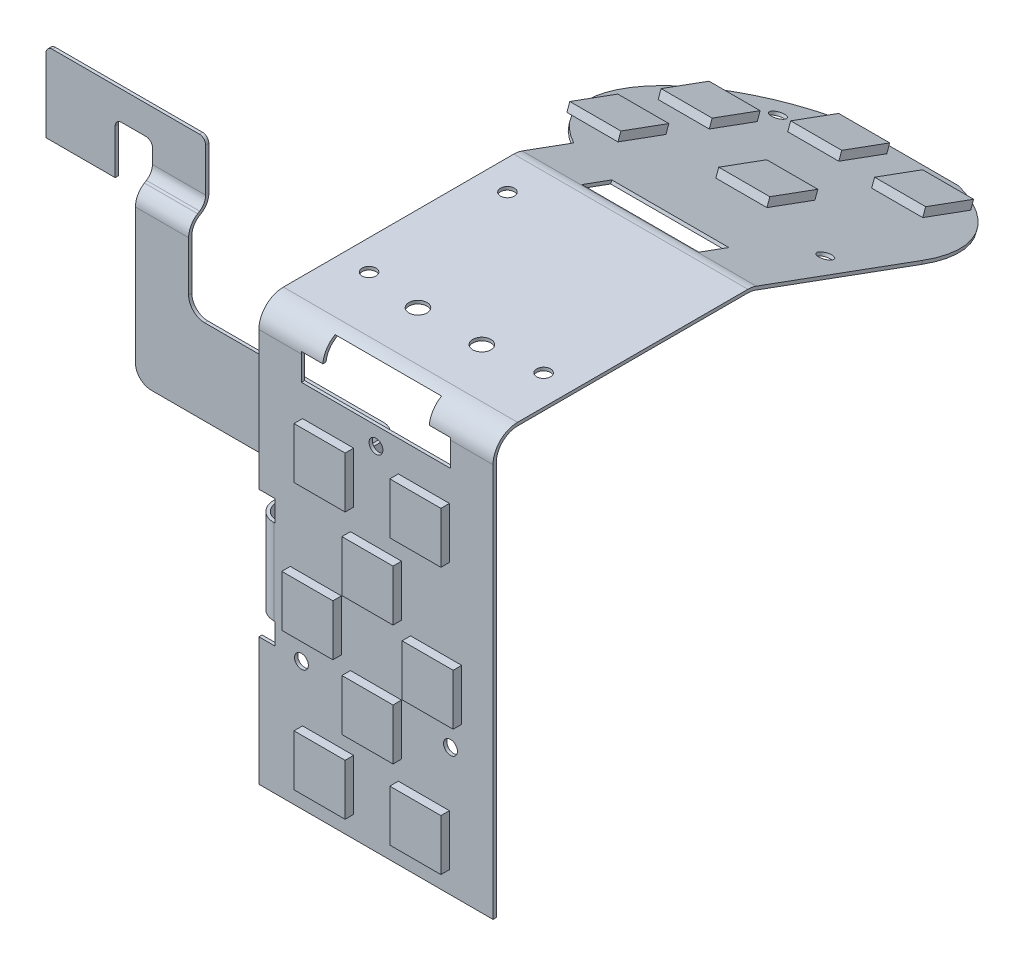
SolidWorks part; units mm, degrees
ref_plane "前视基准面" through (0, 0, 0) normal (0, 0, 1) x (1, 0, 0)
ref_plane "上视基准面" through (0, 0, 0) normal (0, 1, 0) x (1, 0, 0)
ref_plane "右视基准面" through (0, 0, 0) normal (1, 0, 0) x (0, 0, -1)
other "Configuration Table"
sketch "草图1" plane through (0, 0, 0) normal (1, 0, 0) x (0, 0, -1)
  line L0 (0, -25) -> (0, -2)
  line L1 (2, 0) -> (23.6457, 0)
  line L2 (24.3327, -0.1217) -> (52.1746, -10.3049)
  line L3 (-0.3, -25) -> (-0.3, -2)
  line L4 (2, 0.3) -> (23.6457, 0.3)
  line L5 (24.4358, 0.1601) -> (52.2777, -10.0231)
  line L6 (0, -25) -> (-0.3, -25)
  line L7 (52.2777, -10.0231) -> (52.1746, -10.3049)
  arc A0 (23.6457, 0) -> (24.3327, -0.1217) centre (23.6457, -2) cw
  arc A1 (0, -2) -> (2, 0) centre (2, -2) cw
  arc A2 (-0.3, -2) -> (2, 0.3) centre (2, -2) cw
  arc A3 (23.6457, 0.3) -> (24.4358, 0.1601) centre (23.6457, -2) cw
  point P7 (24, 0)
  point P10 (0, 0)
  dimension "D5" = 2
  dimension "D1" = 25
  dimension "D2" = 24
  dimension "D3" = 159.91
  dimension "D4" = 30
  dimension "D6" = 0.3
extrude "凸台-拉伸1" add sketch "草图1" along normal blind 22
sketch "草图2" plane through (0, 0, 0.3) normal (0, 0, 1) x (1, 0, 0)
  line L0 (22, 0.3) -> (0, 0.3) construction
  line L1 (4, -4.3) -> (18, -4.3)
  line L2 (4, -4.3) -> (4, -1.8)
  line L3 (4, -1.8) -> (18, -1.8)
  line L4 (18, -4.3) -> (18, -1.8)
  line L5 (6, -1.8) -> (16, -1.8)
  line L6 (6, -1.8) -> (6, 0)
  line L7 (6, 0) -> (16, 0)
  line L8 (16, -1.8) -> (16, 0)
  line L10 (11, -26.5654) -> (11, 3.7124) construction
  line L12 (0, -2) -> (0, -25) construction
  line L13 (22, -2) -> (22, -25) construction
  line M13 (22, -2) -> (0, -2)
  dimension "D1" = 1.8
  dimension "D2" = 2.5
  dimension "D3" = 0.3
  dimension "D4" = 14
  dimension "D5" = 10
extrude "切除-拉伸1" cut sketch "草图2" against normal blind 4 contours L3 L10 L7 L6 | L10 L5 L8 L7 | L1 L10 L2 M13 | L10 L1 L4 M13 | L10 L3 L2 M13 | L10 L4 L3 L5 M13 region at (7.5, -3.15, 0.3) region at (14.5, -3.15, 0.3) region at (7.5, -1.9, 0.3) region at (14.5, -1.9, 0.3) region at (13.5, -0.9, 0.3) region at (8.5, -0.9, 0.3)
sketch "草图3" plane through (0, 8.024, -2.9348) normal (0, 0.9392, -0.3435) x (1, 0, 0)
  line L0 (22, 52.5397) -> (22, 22.894) construction
  line L1 (22, 52.5397) -> (0, 52.5397) construction
  circle A0 centre (8, 39.5397) radius 14
  line M2 (0, 52.5397) -> (0, 22.894)
  line M4 (22, 22.894) -> (22, 52.5397)
  line M5 (22, 52.5397) -> (0, 52.5397)
  dimension "D1" = 28
  dimension "D2" = 13
extrude "切除-拉伸2" cut sketch "草图3" against normal through all contours A0 M4 M5 | A0 M5 M2 region at (19.6053, -8.9881, -49.4478) region at (0.8895, -9.8577, -51.8254)
extrude "凸台-拉伸2" add sketch "草图3<3>" against normal blind 0.3
sketch "草图3<3>" plane through (0, 8.024, -2.9348) normal (0, 0.9392, -0.3435) x (1, 0, 0) same geometry as "草图3"
sketch "草图4" plane through (0, 0, 0.3) normal (0, 0, 1) x (1, 0, 0)
  line L0 (-5.9466, -22.2) -> (23.7502, -22.2) construction
  line L1 (8.6, -14.15) -> (13.4, -14.15)
  line L2 (8.6, -14.15) -> (8.6, -18.95)
  line L3 (8.6, -18.95) -> (13.4, -18.95)
  line L4 (13.4, -14.15) -> (13.4, -18.95)
  line L5 (11, -28.2671) -> (11, 2.5503) construction
  line L6 (0, -2) -> (0, -25) construction
  line L7 (22, -2) -> (22, -25) construction
  line L8 (22, -25) -> (0, -25) construction
  line L9 (8.6, -25.45) -> (13.4, -25.45)
  line L10 (8.6, -25.45) -> (8.6, -30.25)
  line L11 (8.6, -30.25) -> (13.4, -30.25)
  line L12 (13.4, -25.45) -> (13.4, -30.25)
  line L14 (2.95, -19.8) -> (7.75, -19.8)
  line L15 (2.95, -19.8) -> (2.95, -24.6)
  line L16 (2.95, -24.6) -> (7.75, -24.6)
  line L17 (7.75, -19.8) -> (7.75, -24.6)
  line L18 (14.25, -19.8) -> (19.05, -19.8)
  line L19 (14.25, -19.8) -> (14.25, -24.6)
  line L20 (14.25, -24.6) -> (19.05, -24.6)
  line L21 (19.05, -19.8) -> (19.05, -24.6)
  dimension "D1" = 4.8
  dimension "D2" = 2.8
  dimension "D3" = 6.5
  dimension "D4" = 6.5
extrude "凸台-拉伸3" add sketch "草图4" along normal blind 0.8
sketch "草图5" plane through (0, 0.3, 0) normal (0, 1, 0) x (1, 0, 0)
  line L0 (11, -6.2283) -> (11, 16.6274) construction
  line L3 (0, 23.6457) -> (0, 2) construction
  line L4 (22, 23.6457) -> (22, 2) construction
  line L5 (22, 23.6457) -> (0, 23.6457) construction
  circle A0 centre (8, 6.6457) radius 0.85
  circle A1 centre (14, 6.6457) radius 0.85
  dimension "D1" = 1.7
  dimension "D2" = 17
  dimension "D3" = 3
extrude "切除-拉伸3" cut sketch "草图5" against normal through all
sketch "草图6" plane through (0, 8.024, -2.9348) normal (0, 0.9392, -0.3435) x (1, 0, 0)
  line L0 (11, 16.3664) -> (11, 30.7303) construction
  line L1 (5.5, 23) -> (16.5, 23)
  line L2 (5.5, 23) -> (5.5, 26)
  line L3 (5.5, 26) -> (16.5, 26)
  line L4 (16.5, 23) -> (16.5, 26)
  line L7 (0, 22.1039) -> (0, 1.7753) construction
  line L8 (22, 22.1039) -> (22, 1.7753) construction
  dimension "D1" = 11
  dimension "D2" = 3
  dimension "D3" = 23
extrude "切除-拉伸4" cut sketch "草图6" against normal blind 1
sketch "草图7" plane through (0, 8.024, -2.9348) normal (0, 0.9392, -0.3435) x (1, 0, 0)
  line L1 (7.3385, 34.4514) -> (12.1385, 34.4514)
  line L2 (7.3385, 34.4514) -> (7.3385, 39.2514)
  line L3 (7.3385, 39.2514) -> (12.1385, 39.2514)
  line L4 (12.1385, 34.4514) -> (12.1385, 39.2514)
  line L5 (11.7188, 45.3744) -> (16.5188, 45.3744)
  line L6 (11.7188, 45.3744) -> (11.7188, 50.1744)
  line L7 (11.7188, 50.1744) -> (16.5188, 50.1744)
  line L8 (16.5188, 45.3744) -> (16.5188, 50.1744)
  line L9 (7.6196, 46.4557) -> (2.8196, 46.4557)
  line L10 (7.6196, 46.4557) -> (7.6196, 51.2557)
  line L11 (7.6196, 51.2557) -> (2.8196, 51.2557)
  line L12 (2.8196, 46.4557) -> (2.8196, 51.2557)
  line L13 (0.9105, 40.6376) -> (-3.8895, 40.6376)
  line L14 (0.9105, 40.6376) -> (0.9105, 45.4376)
  line L15 (0.9105, 45.4376) -> (-3.8895, 45.4376)
  line L16 (-3.8895, 40.6376) -> (-3.8895, 45.4376)
  line L17 (0.748, 31.6791) -> (-4.052, 31.6791)
  line L18 (0.748, 31.6791) -> (0.748, 36.4791)
  line L19 (0.748, 36.4791) -> (-4.052, 36.4791)
  line L20 (-4.052, 31.6791) -> (-4.052, 36.4791)
  dimension "D1" = 4.8
extrude "凸台-拉伸4" add sketch "草图7" along normal blind 0.8
sketch "草图9" plane through (0, -25, 0) normal (0, -1, 0) x (1, 0, 0)
  line L0 (22, 0.3) -> (0, 0.3) construction
  line L1 (0, 0) -> (1.5, 0)
  line L2 (0, 0) -> (0, 0.3)
  line L3 (0, 0.3) -> (1.5, 0.3)
  line L4 (1.5, 0) -> (1.5, 0.3)
  dimension "D1" = 1.5
extrude "切除-拉伸5" cut sketch "草图9" against normal blind 10
sketch "草图10" plane through (0, -25, 0) normal (0, -1, 0) x (1, 0, 0)
  line L0 (1.5, 0) -> (1.4, 0)
  line L1 (-0.1, -1.5) -> (-0.1, -11.5)
  line L2 (-1.6, -13) -> (-17.6, -13)
  line L3 (1.5, 0.3) -> (1.4, 0.3)
  line L4 (-0.4, -1.5) -> (-0.4, -11.5)
  line L5 (-1.6, -12.7) -> (-17.6, -12.7)
  line L6 (1.5, 0) -> (1.5, 0.3)
  line L7 (-17.6, -13) -> (-17.6, -12.7)
  arc A0 (1.4, 0) -> (-0.1, -1.5) centre (1.4, -1.5) ccw
  arc A1 (-0.1, -11.5) -> (-1.6, -13) centre (-1.6, -11.5) cw
  arc A2 (1.4, 0.3) -> (-0.4, -1.5) centre (1.4, -1.5) ccw
  arc A3 (-0.4, -11.5) -> (-1.6, -12.7) centre (-1.6, -11.5) cw
  point P8 (-0.1, 0)
  point P11 (-0.1, -13)
  dimension "D3" = 1.5
  dimension "D1" = 1.6
  dimension "D2" = 13
  dimension "D5" = 16
  dimension "D4" = 0.3
extrude "凸台-拉伸5" add sketch "草图10" against normal blind 8
sketch "草图11" plane through (0, 0, -12.7) normal (0, 0, 1) x (1, 0, 0)
  line L0 (-17.6, -17) -> (-17.6, -25)
  line L1 (-17.6, -25) -> (-23.1, -25)
  line L2 (-24.6, -23.5) -> (-24.6, -11)
  line L3 (-24.6, -11) -> (-19.6, -11)
  line L4 (-19.6, -11) -> (-19.6, -15.5)
  line L5 (-18.1, -17) -> (-17.6, -17)
  arc A0 (-23.1, -25) -> (-24.6, -23.5) centre (-23.1, -23.5) cw
  arc A1 (-19.6, -15.5) -> (-18.1, -17) centre (-18.1, -15.5) ccw
  point P10 (-24.6, -25)
  dimension "D4" = 1.5
  dimension "D1" = 7
  dimension "D2" = 14
  dimension "D3" = 5
extrude "凸台-拉伸6" add sketch "草图11" against normal blind 0.3
sketch "草图12" plane through (-24.6, 0, 0) normal (-1, 0, 0) x (0, 0, 1)
  line L0 (-13, -11) -> (-13, -10.8314)
  line L1 (-13.705, -9.5594) -> (-13.895, -9.4406)
  line L2 (-14.6, -8.1686) -> (-14.6, -8)
  line L3 (-12.7, -11) -> (-12.7, -10.8314)
  line L4 (-13.546, -9.305) -> (-13.736, -9.1862)
  line L5 (-14.3, -8.1686) -> (-14.3, -8)
  line L6 (-13, -11) -> (-12.7, -11)
  line L7 (-14.6, -8) -> (-14.3, -8)
  arc A0 (-13, -10.8314) -> (-13.705, -9.5594) centre (-14.5, -10.8314) ccw
  arc A1 (-13.895, -9.4406) -> (-14.6, -8.1686) centre (-13.1, -8.1686) cw
  arc A2 (-12.7, -10.8314) -> (-13.546, -9.305) centre (-14.5, -10.8314) ccw
  arc A3 (-13.736, -9.1862) -> (-14.3, -8.1686) centre (-13.1, -8.1686) cw
  point P8 (-13, -10)
  point P11 (-14.6, -9)
  dimension "D5" = 1.5
  dimension "D1" = 1
  dimension "D2" = 1
  dimension "D3" = 1.6
  dimension "D4" = 1
  dimension "D6" = 0.3
extrude "凸台-拉伸7" add sketch "草图12" against normal blind 5
sketch "草图13" plane through (0, 0, -14.3) normal (0, 0, 1) x (1, 0, 0)
  line L0 (-24.6, -8) -> (-19.6, -8)
  line L1 (-19.6, -8) -> (-19.6, -4.1)
  line L2 (-20.2, -3.5) -> (-34, -3.5)
  line L3 (-34.6, -4.1) -> (-34.6, -11)
  line L4 (-34.6, -11) -> (-28.1, -11)
  line L5 (-28.1, -11) -> (-28.1, -6.8)
  line L6 (-27.5, -6.2) -> (-25.2, -6.2)
  line L7 (-24.6, -6.8) -> (-24.6, -8)
  arc A0 (-34, -3.5) -> (-34.6, -4.1) centre (-34, -4.1) ccw
  arc A1 (-19.6, -4.1) -> (-20.2, -3.5) centre (-20.2, -4.1) ccw
  arc A2 (-25.2, -6.2) -> (-24.6, -6.8) centre (-25.2, -6.8) cw
  arc A3 (-28.1, -6.8) -> (-27.5, -6.2) centre (-27.5, -6.8) cw
  point P12 (-34.6, -3.5)
  point P15 (-19.6, -3.5)
  point P18 (-24.6, -6.2)
  dimension "D5" = 0.6
  dimension "D1" = 4.5
  dimension "D2" = 6.5
  dimension "D3" = 7.5
  dimension "D4" = 1.8
  dimension "D6" = 15
extrude "凸台-拉伸8" add sketch "草图13" against normal blind 0.3
sketch "草图14" plane through (0, 8.024, -2.9348) normal (0, 0.9392, -0.3435) x (1, 0, 0)
  line L0 (0, 28.0506) -> (0, 22.894) construction
  line L1 (2, 52.5506) -> (14, 52.5506)
  line L2 (2, 52.5506) -> (2, 54.5506)
  line L3 (2, 54.5506) -> (14, 54.5506)
  line L4 (14, 52.5506) -> (14, 54.5506)
  circle A0 centre (0.5, 47.9506) radius 0.65
  circle A1 centre (19.5, 32.4506) radius 0.65
  dimension "D5" = 1.3
  dimension "D1" = 12
  dimension "D2" = 2
  dimension "D3" = 24.5
  dimension "D4" = 2
  dimension "D6" = 0.5
  dimension "D7" = 19.9
  dimension "D8" = 19
  dimension "D9" = 15.5
extrude "切除-拉伸6" cut sketch "草图14" against normal blind 4
sketch "草图15" plane through (0, 0.3, 0) normal (0, 1, 0) x (1, 0, 0)
  line L0 (2.8, 18.5921) -> (2.8, 10.622) construction
  line L1 (15.631, 7.25) -> (4.6393, 7.25) construction
  line L4 (11, -5.7583) -> (11, 19.5262) construction
  line L5 (0, 23.6457) -> (0, 2) construction
  line L6 (22, 23.6457) -> (22, 2) construction
  line L7 (22, 2) -> (0, 2) construction
  circle A0 centre (2.8, 20.25) radius 0.65
  circle A1 centre (2.8, 7.25) radius 0.65
  circle A2 centre (19.2, 7.25) radius 0.65
  dimension "D1" = 1.3
  dimension "D2" = 13
  dimension "D3" = 16.4
  dimension "D4" = 5.25
extrude "切除-拉伸7" cut sketch "草图15" against normal blind 4
sketch "草图17" plane through (0, 0, 0.3) normal (0, 0, 1) x (1, 0, 0)
  line L0 (22, -25) -> (22, -39)
  line L1 (22, -39) -> (0, -39)
  line L2 (0, -39) -> (0, -27)
  line L3 (0, -27) -> (1.5, -27)
  line L4 (1.5, -27) -> (1.5, -25)
  line L5 (22, -25) -> (1.4, -25) construction
  line L6 (1.5, -25) -> (22, -25)
  line L7 (1.5, -15) -> (1.5, -17) construction
  dimension "D1" = 2
  dimension "D2" = 14
extrude "凸台-拉伸9" add sketch "草图17" against normal blind 0.3
sketch "草图16" plane through (0, 0, 0.3) normal (0, 0, 1) x (1, 0, 0)
  line L0 (22, -2) -> (22, -39) construction
  line L1 (22, -2) -> (18, -2) construction
  line L2 (4, -27) -> (18, -27) construction
  circle A0 centre (11, -6) radius 0.65
  circle A1 centre (4, -27) radius 0.65
  circle A2 centre (18, -27) radius 0.65
  dimension "D1" = 1.3
  dimension "D2" = 11
  dimension "D3" = 4
  dimension "D4" = 18
  dimension "D5" = 21
  dimension "D6" = 14
extrude "切除-拉伸8" cut sketch "草图16" against normal blind 4
sketch "草图18" plane through (0, 0, 0.3) normal (0, 0, 1) x (1, 0, 0)
  line L0 (11, -23.45) -> (11, -36.7361) construction
  line L1 (4.1, -37) -> (8.9, -37)
  line L2 (4.1, -37) -> (4.1, -32.2)
  line L3 (4.1, -32.2) -> (8.9, -32.2)
  line L4 (8.9, -37) -> (8.9, -32.2)
  line L5 (13.1, -37) -> (17.9, -37)
  line L6 (13.1, -37) -> (13.1, -32.2)
  line L7 (13.1, -32.2) -> (17.9, -32.2)
  line L8 (17.9, -37) -> (17.9, -32.2)
  line L9 (0, -2) -> (0, -15) construction
  line L10 (0, -39) -> (22, -39) construction
  line L11 (4.1, -12) -> (8.9, -12)
  line L12 (4.1, -12) -> (4.1, -7.2)
  line L13 (4.1, -7.2) -> (8.9, -7.2)
  line L14 (8.9, -12) -> (8.9, -7.2)
  line L15 (13.1, -12) -> (17.9, -12)
  line L16 (13.1, -12) -> (13.1, -7.2)
  line L17 (13.1, -7.2) -> (17.9, -7.2)
  line L18 (17.9, -12) -> (17.9, -7.2)
  line L19 (22, -2) -> (22, -39) construction
  dimension "D1" = 4.8
  dimension "D2" = 4.2
  dimension "D3" = 2
  dimension "D4" = 20.2
extrude "凸台-拉伸10" add sketch "草图18" along normal blind 0.8
